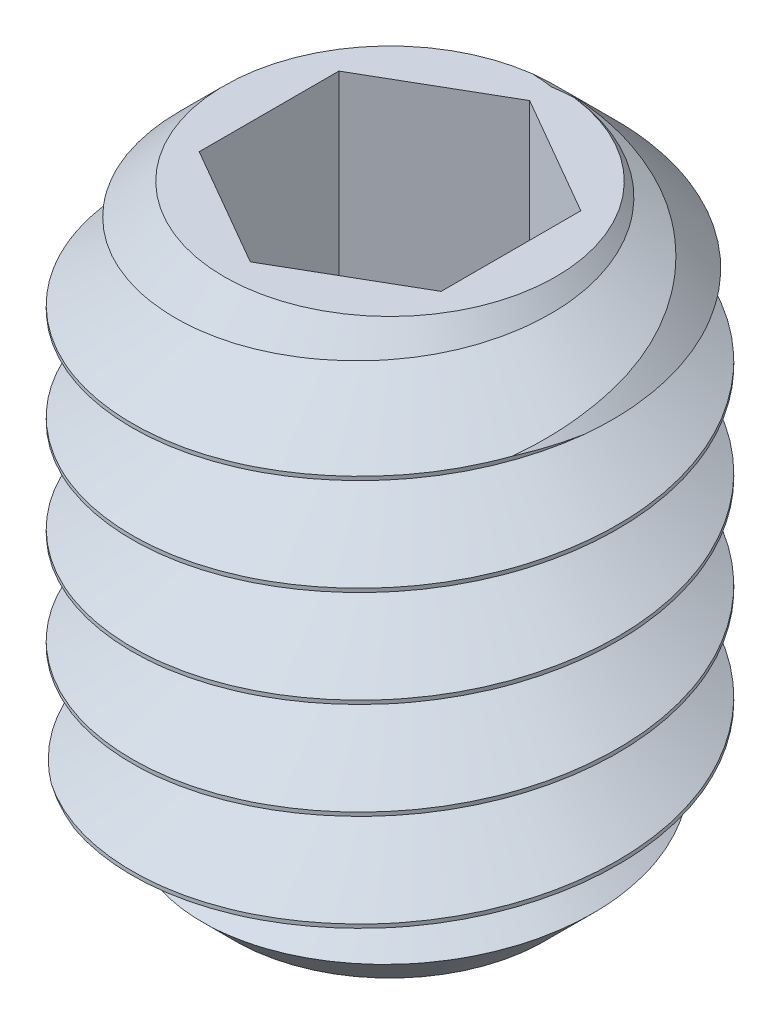
SolidWorks part; units mm, degrees
material "Alloy Steel"
ref_plane "Front Plane" through (0, 0, 0) normal (0, 0, 1) x (1, 0, 0)
ref_plane "Top Plane" through (0, 0, 0) normal (0, 1, 0) x (1, 0, 0)
ref_plane "Right Plane" through (0, 0, 0) normal (1, 0, 0) x (0, 0, -1)
sketch "Sketch1" plane through (0, 0, 0) normal (0, 0, 1) x (1, 0, 0)
  line L0 (0, 0) -> (0, 54.6222) construction
  line L1 (0, 0.5866) -> (-1.016, 0)
  line L2 (-1.016, 0) -> (-1.27, 0)
  line L3 (-1.27, 0) -> (-1.9939, 0.7239)
  line L4 (-1.9939, 0.7239) -> (-1.9939, 4.1275)
  line L5 (-1.9939, 4.1275) -> (-1.3589, 4.7625)
  line L6 (-1.3589, 4.7625) -> (0, 4.7625)
  line L7 (0, 4.7625) -> (0, 0.5866)
  dimension "D1" = 60
  dimension "D2" = 2.032
  dimension "D3" = 135
  dimension "D4" = 135
  dimension "D5" = 0.635
  dimension "D6" = 3.9878
  dimension "D7" = 0.254
  dimension "D8" = 4.7625
revolve "Revolve1" add sketch "Sketch1" angle 360 about L0
sketch "Sketch2" plane through (0, 4.7625, 0) normal (0, 1, 0) x (1, 0, 0)
  line L0 (0, 0) -> (0, 1.3178) construction
  line L1 (0, 1.1457) -> (-0.9922, 0.5728)
  line L2 (-0.9922, 0.5728) -> (-0.9922, -0.5728)
  line L3 (-0.9922, -0.5728) -> (0, -1.1457)
  line L4 (0, -1.1457) -> (0.9922, -0.5728)
  line L5 (0.9922, -0.5728) -> (0.9922, 0.5728)
  line L6 (0.9922, 0.5728) -> (0, 1.1457)
  circle A0 centre (0, 0) radius 0.9922 construction
  dimension "D1" = 1.9844
extrude "Cut-Extrude1" cut sketch "Sketch2" against normal blind 1.778
sketch "Sketch3" plane through (0, 4.7625, 0) normal (0, 1, 0) x (1, 0, 0)
  circle A0 centre (0, 0) radius 1.9939 construction
  circle A1 centre (0, 0) radius 1.9939
curve "Helix/Spiral1" pitch 0.795 height 9.525 radius 1.9939 centre (0, 4.7625, 0) axis (0, -1, 0) start towards (0, 0, 1)
sketch "Sketch4" plane through (0, 0, 0) normal (1, 0, 0) x (0, 0, -1)
  line L0 (-2.0193, 5.5562) -> (-2.0193, 4.7625)
  line L1 (-2.0193, 4.7625) -> (-1.3319, 5.1594)
  line L2 (-1.3319, 5.1594) -> (-2.0193, 5.5562)
  line L3 (-1.3319, 5.1594) -> (-2.0193, 5.1594) construction
  line L5 (-2.0193, 5.5562) -> (-1.3319, 5.9531) construction
  line L6 (-1.3319, 5.9531) -> (-2.0193, 6.35) construction
  line L7 (-2.0193, 6.35) -> (-2.0193, 5.5562) construction
  line L8 (1.3589, 4.7625) -> (-1.3589, 4.7625) construction
  line L10 (0, 4.7625) -> (0, 10.7636) construction
  dimension "D1" = 60
  dimension "D2" = 0.7937
  dimension "D3" = 4.0386
sweep "Cut-Sweep3" cut profiles "Sketch4" path "Helix/Spiral1" align with end faces yes
